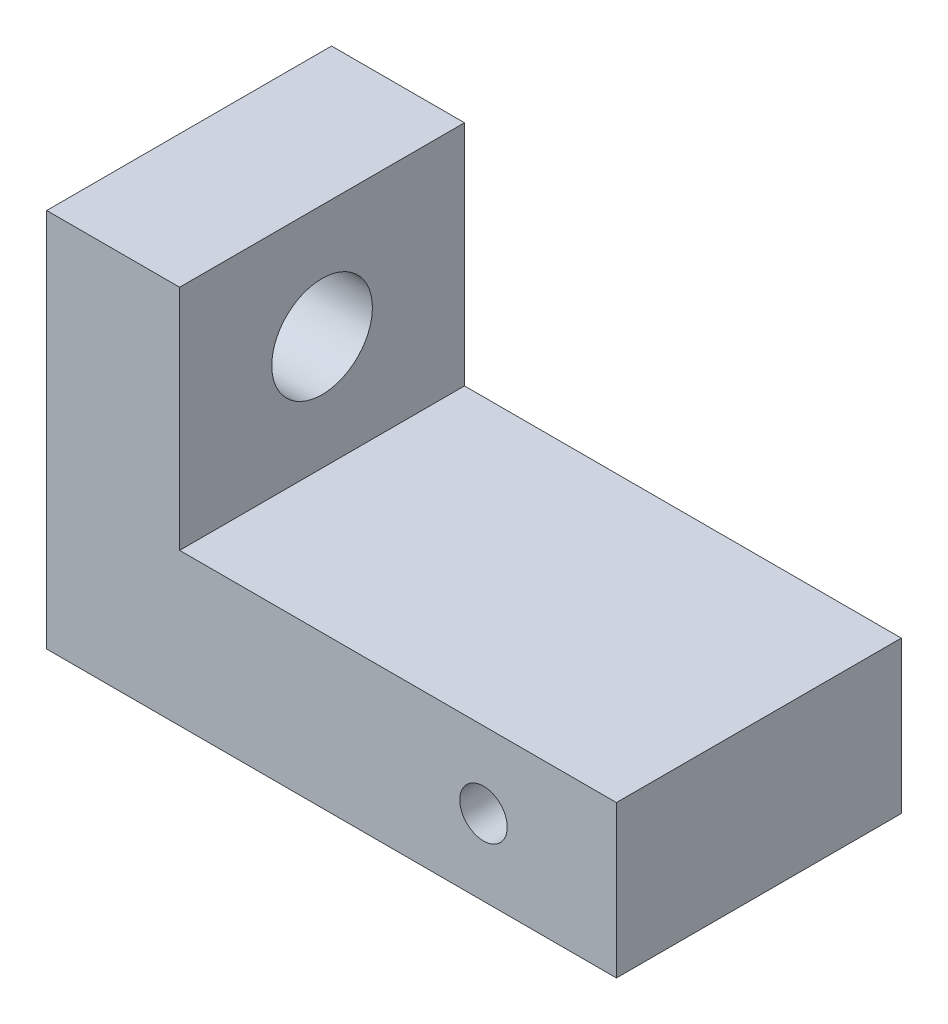
SolidWorks part; units mm, degrees
ref_plane "Front Plane" through (0, 0, 0) normal (0, 0, 1) x (1, 0, 0)
ref_plane "Top Plane" through (0, 0, 0) normal (0, 1, 0) x (1, 0, 0)
ref_plane "Right Plane" through (0, 0, 0) normal (1, 0, 0) x (0, 0, -1)
sketch "Sketch1" plane through (0, 0, 0) normal (0, 0, 1) x (1, 0, 0)
  line L0 (0, 0) -> (30, 0)
  line L1 (30, 0) -> (30, 8)
  line L2 (30, 8) -> (7, 8)
  line L3 (7, 8) -> (7, 20)
  line L4 (7, 20) -> (0, 20)
  line L5 (0, 20) -> (0, 0)
  dimension "D1" = 30
  dimension "D2" = 8
  dimension "D3" = 7
  dimension "D4" = 20
extrude "Boss-Extrude1" add sketch "Sketch1" along normal blind 15
sketch "Sketch3" plane through (7, 0, 0) normal (1, 0, 0) x (0, 0, -1)
  line L0 (-7.5, 20) -> (-7.5, 8) construction
  line L1 (-15, 20) -> (0, 20) construction
  line L2 (-15, 8) -> (0, 8) construction
  line L3 (0, 14) -> (-15, 14) construction
  line L4 (0, 8) -> (0, 20) construction
  line L5 (-15, 8) -> (-15, 20) construction
  circle A0 centre (-7.5, 14) radius 2.65
  dimension "D1" = 5.3
extrude "Cut-Extrude1" cut sketch "Sketch3" against normal blind 15
sketch "Sketch4" plane through (0, 0, 15) normal (0, 0, 1) x (1, 0, 0)
  line L0 (30, 4) -> (0, 4) construction
  line L1 (30, 0) -> (30, 8) construction
  line L2 (0, 20) -> (0, 0) construction
  point P6 (23, 4)
  dimension "D1" = 7
hole_wizard "M3 Tapped Hole1" positions "3DSketch1" profile "Sketch6" tap size "M3" standard "DIN" end condition through all
sketch3d "3DSketch1"
  point P0 (23, 4, 15)
sketch "Sketch6" plane through (23, 4, 15) normal (1, 0, 0) x (0, -1, 0)
  line L0 (0, 0) -> (0, 15)
  line L1 (0, 15) -> (1.25, 15)
  line L2 (1.25, 15) -> (1.25, 0)
  line L5 (1.25, 0) -> (0, 0)
  line L11 (0, -6.35) -> (0, 107.95) construction
  dimension "Thru Tap Drill Dia." = 2.5
  dimension "Thru Tap Drill Depth" = 15
cosmetic thread "Hole Thread1" parameters "D2"=3
